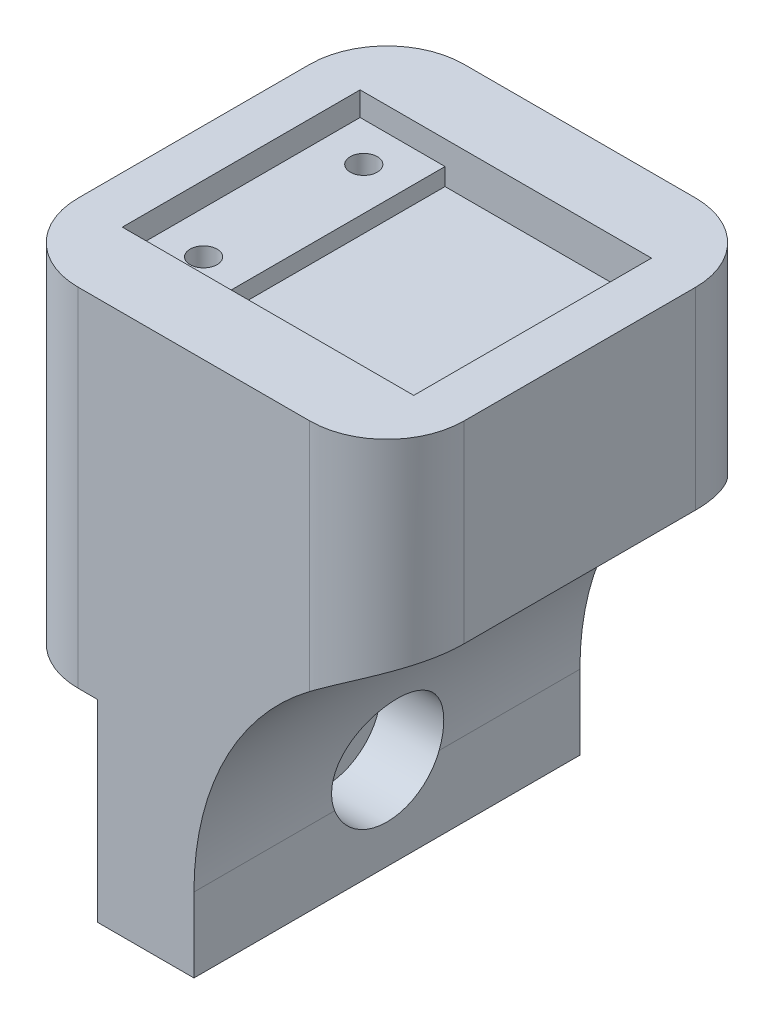
SolidWorks part; units mm, degrees
ref_plane "Front Plane" through (0, 0, 0) normal (0, 0, 1) x (1, 0, 0)
ref_plane "Top Plane" through (0, 0, 0) normal (0, 1, 0) x (1, 0, 0)
ref_plane "Right Plane" through (0, 0, 0) normal (1, 0, 0) x (0, 0, -1)
sketch "Profile" plane through (0, 0, 0) normal (0, 0, 1) x (1, 0, 0)
  line L1 (-6.35, 22.86) -> (6.35, 22.86)
  line L2 (-6.35, 22.86) -> (-6.35, 0)
  line L3 (-6.35, 0) -> (6.35, 0)
  line L4 (6.35, 22.86) -> (6.35, 0)
  line L5 (0, 0) -> (6.35, 0)
  line L6 (0, 0) -> (0, -12.7)
  line L7 (0, -12.7) -> (6.35, -12.7)
  line L8 (6.35, 0) -> (6.35, -12.7)
  dimension "D1" = 22.86
  dimension "D2" = 12.7
  dimension "D3" = 6.35
  dimension "D4" = 12.7
extrude "Boss-Extrude1" add sketch "Profile" along normal mid plane 25.4 contours L4 L1 L2 L3 | L8 L3 L6 L7 region at (0, 11.43, 0) region at (3.175, -6.35, 0)
sketch "ScrewHole" plane through (0, 0, 0) normal (-1, 0, 0) x (0, 0, 1)
  line L1 (12.7, -12.7) -> (-12.7, -12.7) construction
  line L2 (12.7, 0) -> (-12.7, 0) construction
  circle A0 centre (0, -6.477) radius 2.159
  point P2 (0, 0)
  point P10 (0, -12.7)
  dimension "D1" = 4.318
  dimension "D2" = 6.477
extrude "Cut-Extrude1" cut sketch "ScrewHole" against normal through all both
sketch "Sketch3" plane through (6.35, 0, 0) normal (1, 0, 0) x (0, 0, -1)
  circle A0 centre (0, -6.477) radius 2.159 construction
  circle A1 centre (0, -6.477) radius 2.159
  circle A2 centre (0, -6.477) radius 3.683
  dimension "D1" = 7.366
extrude "Cut-Extrude2" cut sketch "Sketch3" against normal blind 4.064
sketch "Sketch4" plane through (6.35, 0, 0) normal (1, 0, 0) x (0, 0, -1)
  line L0 (12.7, 22.86) -> (12.7, -12.7) construction
  line L1 (-12.7, 22.86) -> (12.7, 22.86)
  line L2 (-12.7, 22.86) -> (-12.7, 10.16)
  line L3 (-12.7, 10.16) -> (12.7, 10.16)
  line L4 (12.7, 22.86) -> (12.7, 10.16)
  dimension "D1" = 12.7
extrude "Boss-Extrude2" add sketch "Sketch4" along normal blind 12.7
sketch "Sketch6" plane through (0, 22.86, 0) normal (0, 1, 0) x (1, 0, 0)
  line L0 (-6.35, -12.7) -> (-6.35, 12.7) construction
  line L1 (-3.2385, 7.8232) -> (15.9385, 7.8232)
  line L2 (-3.2385, 7.8232) -> (-3.2385, -7.8232)
  line L3 (-3.2385, -7.8232) -> (15.9385, -7.8232)
  line L4 (15.9385, 7.8232) -> (15.9385, -7.8232)
  line L5 (-6.35, -12.7) -> (19.05, -12.7) construction
  point P6 (-6.35, 0)
  point P7 (-3.2385, 0)
  point P10 (6.35, -12.7)
  point P11 (6.35, -7.8232)
  dimension "D1" = 19.177
  dimension "D2" = 15.6464
extrude "Cut-Extrude3" cut sketch "Sketch6" against normal blind 1.5748
sketch "Sketch7" plane through (0, 21.2852, 0) normal (0, 1, 0) x (1, 0, 0)
  line L0 (13.1445, 5.2705) -> (13.1445, -5.2705) construction
  line L1 (15.9385, -7.8232) -> (15.9385, 7.8232) construction
  line L2 (6.35, 7.8232) -> (6.35, -7.8232) construction
  line L3 (15.9385, 7.8232) -> (-3.2385, 7.8232) construction
  line L4 (-3.2385, -7.8232) -> (15.9385, -7.8232) construction
  circle A0 centre (13.1445, 5.2705) radius 0.889
  circle A1 centre (13.1445, -5.2705) radius 0.889
  circle A2 centre (-0.4445, -5.2705) radius 0.889
  circle A3 centre (-0.4445, 5.2705) radius 0.889
  point P6 (15.9385, 0)
  point P7 (13.1445, 0)
  dimension "D3" = 1.778
  dimension "D4" = 1.778
  dimension "D1" = 10.541
  dimension "D2" = 2.794
ref_plane "Plane1" through (6.35, 0, 0) normal (1, 0, 0) x (0, 0, -1)
sketch "Sketch9" plane through (0, 21.2852, 0) normal (0, 1, 0) x (1, 0, 0)
  line L0 (-3.2385, -7.8232) -> (15.9385, -7.8232) construction
  line L1 (2.3495, 7.8232) -> (15.9385, 7.8232)
  line L2 (2.3495, 7.8232) -> (2.3495, -7.8232)
  line L3 (2.3495, -7.8232) -> (15.9385, -7.8232)
  line L4 (15.9385, 7.8232) -> (15.9385, -7.8232)
  line L7 (15.9385, -7.8232) -> (15.9385, 7.8232) construction
  line L8 (-3.2385, 7.8232) -> (-3.2385, -7.8232) construction
  line L9 (15.9385, 7.8232) -> (-3.2385, 7.8232) construction
  dimension "D1" = 5.588
extrude "Cut-Extrude5" cut sketch "Sketch9" against normal blind 1.143
extrude "Cut-Extrude6" cut sketch "Sketch7" against normal blind 12.7 contours A2 | A3
fillet "Fillet1" radius 19.05 1 edges at (6.35, 10.16, 0)
fillet "Fillet2" radius 5.08 4 edges at (-6.35, 11.43, -12.7) (19.05, 16.51, -12.7) (-6.35, 11.43, 12.7) (19.05, 16.51, 12.7)
